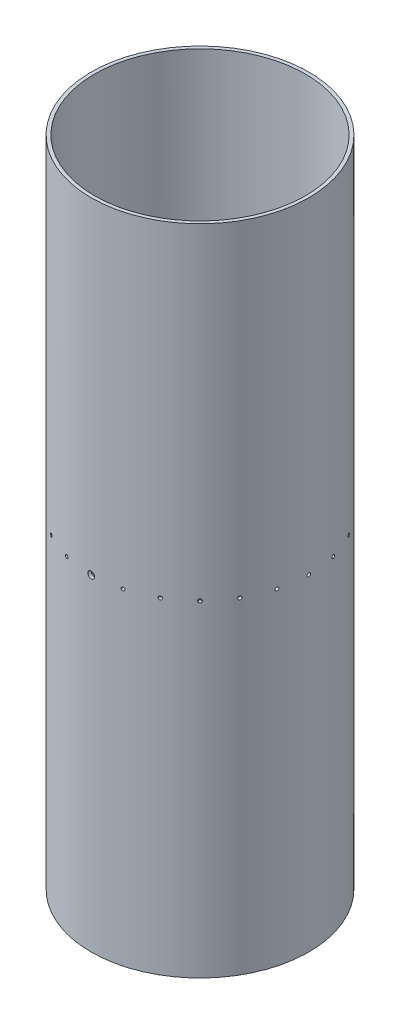
SolidWorks part; units mm, degrees
ref_plane "Front Plane" through (0, 0, 0) normal (0, 0, 1) x (1, 0, 0)
ref_plane "Top Plane" through (0, 0, 0) normal (0, 1, 0) x (1, 0, 0)
ref_plane "Right Plane" through (0, 0, 0) normal (1, 0, 0) x (0, 0, -1)
sketch "Sketch1" plane through (0, 0, 0) normal (0, 1, 0) x (1, 0, 0)
  circle A0 centre (0, 0) radius 101.6
  circle A1 centre (0, 0) radius 98.425
  dimension "D1" = 203.2
  dimension "D2" = 196.85
extrude "Boss-Extrude1" add sketch "Sketch1" along normal blind 609.6
sketch "Sketch2" plane through (0, 0, 0) normal (0, 0, 1) x (1, 0, 0)
  circle A0 centre (0, 304.8) radius 3.175
  dimension "D2" = 6.35
extrude "Cut-Extrude1" cut sketch "Sketch2" against normal through all and the other way through all
sketch "Sketch3" plane through (0, 0, 0) normal (1, 0, 0) x (0, 0, -1)
  circle A0 centre (0, 304.8) radius 1.5875
  dimension "D2" = 3.175
extrude "Cut-Extrude2" cut sketch "Sketch3" against normal blind 609.6
sketch "Sketch4" plane through (0, 0, 0) normal (0, 0, 1) x (1, 0, 0)
  line L0 (0, 0) -> (0, 635.0243) construction
pattern_circular "CirPattern1" count 24 over 360 about axis through (0, 0, 0) along (0, 1, 0) of "Cut-Extrude2" reverse direction yes
